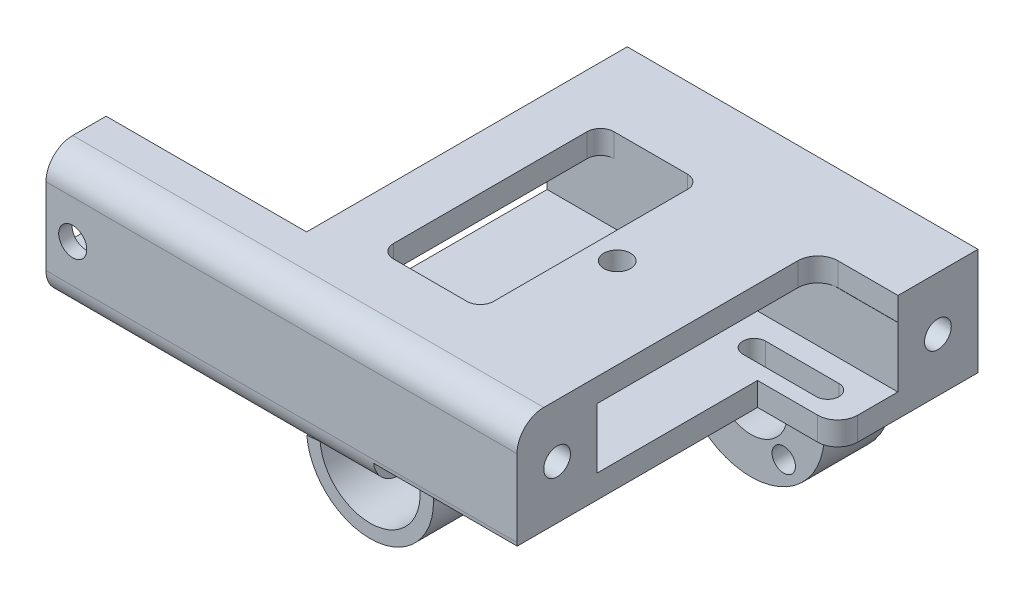
SolidWorks part; units mm, degrees
ref_plane "Front Plane" through (0, 0, 0) normal (0, 0, 1) x (1, 0, 0)
ref_plane "Top Plane" through (0, 0, 0) normal (0, 1, 0) x (1, 0, 0)
ref_plane "Right Plane" through (0, 0, 0) normal (1, 0, 0) x (0, 0, -1)
sketch "Sketch1" plane through (0, 0, 0) normal (0, 0, 1) x (1, 0, 0)
  line L0 (0, 0) -> (0, -35)
  line L1 (0, -35) -> (19, -35)
  line L2 (19, -35) -> (19, -16)
  line L3 (19, -16) -> (52.5, -16)
  line L4 (52.5, -16) -> (52.5, 0)
  line L5 (52.5, 0) -> (0, 0)
  line L6 (0, 0) -> (0.6966, -0.1385)
  dimension "D1" = 35
  dimension "D2" = 19
  dimension "D3" = 52.5
  dimension "D4" = 16
extrude "Boss-Extrude1" add sketch "Sketch1" along normal blind 57 contours L4 L5 L0 L1 L2 L3 region at (21.2152, -13.2602, 0)
ref_plane "Plane1" through (0, 0, 50) normal (0, 0, 1) x (1, 0, 0)
sketch "Sketch3" plane through (0, 0, 0) normal (-1, 0, 0) x (0, 0, 1)
  line L0 (57, 0) -> (0, 0) construction
  line L1 (12, -3.5) -> (45, -3.5)
  line L2 (12, -3.5) -> (12, -12.5)
  line L3 (12, -12.5) -> (45, -12.5)
  line L4 (45, -3.5) -> (45, -12.5)
  line L5 (57, -35) -> (48, -35)
  line L6 (57, -35) -> (57, -19.5)
  line L7 (57, -19.5) -> (48, -19.5)
  line L8 (48, -35) -> (48, -19.5)
  line L9 (0, 0) -> (0, -35) construction
  line L14 (57, -35) -> (0, -35) construction
  dimension "D1" = 9
  dimension "D2" = 33
  dimension "D3" = 3.5
  dimension "D4" = 12
  dimension "D5" = 15.5
  dimension "D6" = 9
extrude "Cut-Extrude2" cut sketch "Sketch3" against normal through all
fillet "Fillet1" radius 4 2 edges at (26.25, 0, 57) (9.5, -19.5, 57)
sketch "Sketch4" plane through (0, 0, 0) normal (0, 0, -1) x (-1, 0, 0)
  line L0 (-9.5, -25.5) -> (-9.5, -35) construction
  line L1 (0, -35) -> (-19, -35) construction
  line L2 (-2.0103, -25.1075) -> (-0.013, -25.0028)
  line L3 (0, -35) -> (-19, -35)
  line L4 (0, -35) -> (0, -16)
  line L5 (0, -16) -> (-19, -16)
  line L6 (-19, -35) -> (-19, -16)
  line L7 (-2.0285, -26.1537) -> (-0.0362, -26.328)
  line L8 (-2.0285, -26.1537) -> (-9.5, -25.5) construction
  line L9 (-0.013, -25.0028) -> (0, -25.0021)
  circle A0 centre (-9.5, -25.5) radius 7.5
  circle A1 centre (-9.5, -25.5) radius 9.5
  line M8 (-19, -35) -> (0, -35)
  line M9 (0, -35) -> (0, 0)
  dimension "D1" = 15
  dimension "D2" = 19
  dimension "D3" = 8
  dimension "D4" = 85
extrude "Cut-Extrude3" cut sketch "Sketch4" against normal through all contours A0 | A1 L6 M8 | L7 A1 L2 A0 | A1 L3 M9 | A1 L4 L9 region at (0.969, -25.6489, 0) region at (9.5, -25.5, 0) region at (0.0039, -25.1268, 0) region at (2.122, -32.878, 0) region at (16.878, -32.878, 0)
sketch "Sketch5" plane through (0, -16, 0) normal (0, -1, 0) x (1, 0, 0)
  line L0 (28, 28.5) -> (32, 28.5) construction
  line L1 (22, 45) -> (26, 45) construction
  line L2 (20, 43) -> (20, 14) construction
  line L3 (22, 12) -> (26, 12) construction
  line L4 (28, 43) -> (28, 14) construction
  line L5 (36, 17) -> (47, 17) construction
  line L6 (36, 18.7) -> (47, 18.7)
  line L7 (36, 15.3) -> (47, 15.3)
  line L8 (19, 56.9686) -> (19, 0) construction
  line L10 (19, 0) -> (52.5, 0) construction
  line L11 (52.5, 0) -> (52.5, 18) construction
  line L12 (52.5, 56.9686) -> (52.5, 0) construction
  line L13 (0, 57) -> (52.5, 57) construction
  line L14 (49.5, 18) -> (49.5, 21) construction
  line L15 (49.5, 21) -> (40.5, 21)
  line L16 (40.5, 21) -> (40.5, 57)
  line L18 (40.5, 57) -> (52.5, 57)
  line L19 (52.5, 57) -> (52.5, 18)
  arc A0 (20, 14) -> (22, 12) centre (22, 14) ccw construction
  arc A1 (26, 12) -> (28, 14) centre (26, 14) ccw construction
  arc A2 (28, 43) -> (26, 45) centre (26, 43) ccw construction
  arc A3 (22, 45) -> (20, 43) centre (22, 43) ccw construction
  circle A4 centre (32, 28.5) radius 2 construction
  arc A5 (36, 18.7) -> (36, 15.3) centre (36, 17) ccw
  arc A6 (47, 15.3) -> (47, 18.7) centre (47, 17) ccw
  arc A7 (52.5, 18) -> (49.5, 21) centre (49.5, 18) ccw
  point P17 (41.5, 17)
  line M12 (52.5, 0) -> (52.5, 56.9686)
  dimension "D1" = 2
  dimension "D4" = 4
  dimension "D6" = 1.7
  dimension "D9" = 2.3
  dimension "D12" = 6
  dimension "D2" = 8
  dimension "D3" = 33
  dimension "D5" = 4
  dimension "D7" = 11
  dimension "D8" = 1
  dimension "D10" = 12
  dimension "D11" = 18
  dimension "D13" = 9
  dimension "D14" = 4.5
extrude "Cut-Extrude4" cut sketch "Sketch5" against normal up to surface (12.5 mm away) contours A4 | L7 A6 L6 A5 | A7 L16 L15 M12 | L19 L18 L16 | L2 A0 L3 A1 L4 A2 L1 A3 region at (41.5, -16, 17) region at (46.5237, -16, 38.9169) up to face at (26.25, -3.5, 28.5)
sketch "Sketch6" plane through (0, 0, 0) normal (0, 1, 0) x (1, 0, 0)
  line L0 (52.5, 0) -> (0, 0) construction
  line L1 (10, -12) -> (21, -12)
  line L2 (8, -14) -> (8, -43)
  line L3 (10, -45) -> (21, -45)
  line L4 (23, -14) -> (23, -43)
  line L5 (0, -53) -> (0, 0) construction
  line L6 (52.5, -56.9686) -> (40.5, -56.9686) construction
  line L7 (43.5, -11.9686) -> (52.5, -11.9686)
  line L8 (40.5, -14.9686) -> (40.5, -56.9686)
  line L9 (40.5, -56.9686) -> (52.5, -56.9686)
  line L10 (52.5, -11.9686) -> (52.5, -56.9686)
  line L11 (52.5, -53) -> (52.5, 0) construction
  line L12 (27, -28.5) -> (23, -28.5) construction
  arc A0 (10, -45) -> (8, -43) centre (10, -43) cw
  arc A1 (23, -43) -> (21, -45) centre (21, -43) cw
  arc A2 (23, -14) -> (21, -12) centre (21, -14) ccw
  arc A3 (10, -12) -> (8, -14) centre (10, -14) ccw
  arc A4 (43.5, -11.9686) -> (40.5, -14.9686) centre (43.5, -14.9686) ccw
  circle A5 centre (27, -28.5) radius 2 construction
  point P6 (8, -45)
  point P11 (23, -12)
  point P14 (8, -12)
  point P25 (40.5, -11.9686)
  dimension "D3" = 2
  dimension "D8" = 3
  dimension "D9" = 4
  dimension "D10" = 4
  dimension "D1" = 33
  dimension "D2" = 15
  dimension "D4" = 12
  dimension "D5" = 8
  dimension "D6" = 45
  dimension "D7" = 12
extrude "Cut-Extrude5" cut sketch "Sketch6" against normal up to surface (3.5 mm away) up to face at (31, -3.5, 37.9895)
sketch "Sketch9" plane through (0, -3.5, 0) normal (0, -1, 0) x (1, 0, 0)
  line L0 (40.5, 21) -> (40.5, 56.9686) construction
  line L1 (19, 0) -> (52.5, 0) construction
  circle A0 centre (27, 28.5) radius 3.2
  dimension "D1" = 6.4
  dimension "D2" = 13.5
  dimension "D3" = 28.5
ref_plane "Plane3" through (0, -5, 0) normal (0, -1, 0) x (-1, 0, 0)
sketch "Sketch10" plane through (0, -5, 0) normal (0, -1, 0) x (-1, 0, 0)
  circle A0 centre (-27, -28.5) radius 2.8
  dimension "D1" = 5.6
loft "Loft1" add profiles "Sketch9", "Sketch10" connector at (30.0985, -3.5, 27.7003) connector at (29.7453, -5, 27.9494)
ref_plane "Plane4" through (0, -8, 0) normal (0, -1, 0) x (-1, 0, 0)
mirror "Mirror2" about plane through (0, -8, 0) normal (0, -1, 0) of "Loft1"
sketch "Sketch11" plane through (0, -11, 0) normal (0, 1, 0) x (1, 0, 0)
  circle A0 centre (27, -28.5) radius 2 construction
  circle A1 centre (27, -28.5) radius 2
extrude "Cut-Extrude6" cut sketch "Sketch11" against normal through all both and the other way through all
sketch "Sketch13" plane through (52.5, 0, 0) normal (1, 0, 0) x (0, 0, -1)
  line L0 (-51, -8) -> (-6, -8) construction
  line L1 (-6, -8) -> (0, -8) construction
  line L2 (0, -16) -> (0, 0) construction
  line L3 (-51, -8) -> (-57, -8) construction
  line L4 (-57, -4) -> (-57, -15.5) construction
  circle A0 centre (-6, -8) radius 2
  circle A1 centre (-51, -8) radius 2
  dimension "D1" = 45
  dimension "D2" = 4
extrude "Cut-Extrude7" cut sketch "Sketch13" against normal blind 20
sketch "Sketch14" plane through (0, 0, 0) normal (0, 0, -1) x (-1, 0, 0)
  line L0 (-28.5, -25.5) -> (-9.5, -25.5) construction
  line L1 (-28.5, -25.5) -> (-28.5, -14.5) construction
  line L2 (-23.5747, -19.1959) -> (-33.4253, -31.8041) construction
  line L3 (-34.8041, -20.5747) -> (-22.1959, -30.4253) construction
  line L4 (-28.5, -14.5) -> (-17.5, -14.5)
  line L5 (-17.5, -14.5) -> (-17.5, -25.5)
  circle A0 centre (-28.5, -25.5) radius 11
  circle A1 centre (-28.5, -25.5) radius 5.5
  circle A2 centre (-28.5, -25.5) radius 8 construction
  circle A3 centre (-23.5747, -19.1959) radius 1.75
  circle A4 centre (-34.8041, -20.5747) radius 1.75
  circle A5 centre (-33.4253, -31.8041) radius 1.75
  circle A6 centre (-22.1959, -30.4253) radius 1.75
  line M8 (-52.5, -16) -> (-19, -16)
  line M9 (-19, -16) -> (-19, -25.5)
  arc M10 (-19, -25.5) -> (-0.0362, -26.328) centre (-9.5, -25.5) ccw
  dimension "D1" = 19
  dimension "D2" = 22
  dimension "D3" = 11
  dimension "D4" = 38
  dimension "D5" = 3.5
  dimension "D6" = 16
extrude "Boss-Extrude2" add sketch "Sketch14" against normal blind 10 contours A0 A6 A5 A4 A3 A1 M9 M8 M10 | A0 M9 M8 region at (20.2019, -17.2019, 0) region at (20.9309, -17.9309, 0)
sketch "Sketch15" plane through (0, 0, 0) normal (-1, 0, 0) x (0, 0, 1)
  line L0 (53, 0) -> (0, 0) construction
  line L1 (53, -19.5) -> (48, -19.5)
  line L2 (57, -15.5) -> (57, -4)
  line L3 (53, 0) -> (48, 0)
  line L4 (48, -19.5) -> (48, 0)
  line L5 (57, -4) -> (57, -15.5) construction
  arc A0 (53, -19.5) -> (57, -15.5) centre (53, -15.5) ccw
  arc A1 (57, -4) -> (53, 0) centre (53, -4) ccw
  point P4 (48, -19.5)
  point P10 (48, 0)
  point P13 (57, -15.5)
  point P14 (59.5216, -15.5)
  dimension "D1" = 4
extrude "Boss-Extrude3" add sketch "Sketch15" along normal blind 30 contours A0 L2 A1 L3 L4 L1
ref_plane "Plane5" through (0, 0, 55) normal (0, 0, 1) x (1, 0, 0)
sketch "Sketch16" plane through (0, 0, 55) normal (0, 0, 1) x (1, 0, 0)
  line L0 (-30, -9.75) -> (-25, -9.75) construction
  line L1 (-30, -15.5) -> (-30, -4) construction
  line L2 (-27.0785, -6.15) -> (-30, -6.15)
  line L3 (-22.9215, -13.35) -> (-20.8431, -9.75)
  line L4 (-20.8431, -9.75) -> (-22.9215, -6.15)
  line L5 (-22.9215, -6.15) -> (-27.0785, -6.15)
  line L6 (-27.0785, -6.15) -> (-29.1569, -9.75)
  line L7 (-29.1569, -9.75) -> (-27.0785, -13.35)
  line L8 (-27.0785, -13.35) -> (-22.9215, -13.35)
  line L9 (-30, -6.15) -> (-30, -13.35)
  line L10 (-30, -13.35) -> (-27.0785, -13.35)
  circle A0 centre (-25, -9.75) radius 3.6 construction
  circle A2 centre (-26, -9.75) radius 2.1
  dimension "D2" = 7.2
  dimension "D3" = 4.2
  dimension "D1" = 5
  dimension "D4" = 4
extrude "Cut-Extrude8" cut sketch "Sketch16" against normal blind 3.4 contours L9 L10 L7 L6 L2 | L7 L8 L3 L4 L5 L6 region at (-28.185, -7.9111, 55) region at (-25, -6.26, 55)
sketch "Sketch18" plane through (0, 0, 57) normal (0, 0, 1) x (1, 0, 0)
  line L4 (-30, -15.5) -> (40.5, -15.5)
  line L5 (40.5, -15.5) -> (40.5, -4)
  line L6 (40.5, -4) -> (-30, -4)
  line L7 (-30, -4) -> (-30, -15.5)
  line L8 (-30, -15.5) -> (40.5, -15.5)
  line L9 (40.5, -15.5) -> (40.5, -4)
  line L10 (40.5, -4) -> (-30, -4)
  line L11 (-30, -4) -> (-30, -15.5)
  circle A2 centre (-26, -9.75) radius 2.1 construction
  circle A3 centre (-26, -9.75) radius 2.1
  dimension "D1" = 0
extrude "Cut-Extrude9" cut sketch "Sketch18" against normal up to surface (9 mm away) contours A3 region at (-26, -9.75, 57) up to face at (-15, -9.75, 48)
